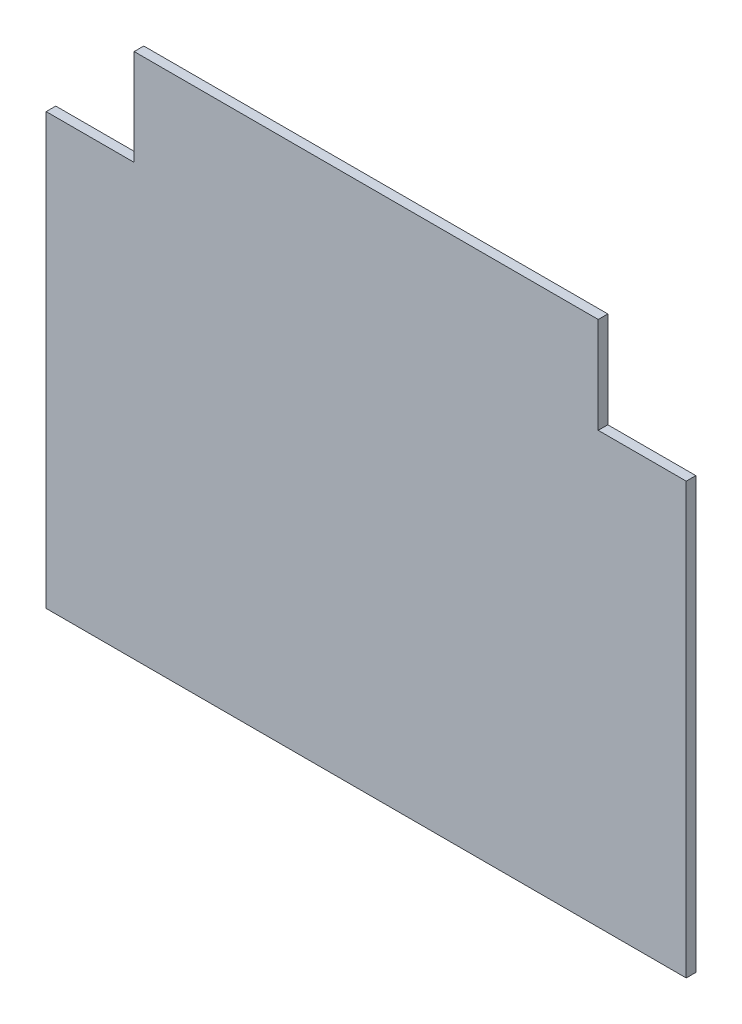
SolidWorks part; units mm, degrees
material "Pine"
ref_plane "Front Plane" through (0, 0, 0) normal (0, 0, 1) x (1, 0, 0)
ref_plane "Top Plane" through (0, 0, 0) normal (0, 1, 0) x (1, 0, 0)
ref_plane "Right Plane" through (0, 0, 0) normal (1, 0, 0) x (0, 0, -1)
sketch "Sketch1" plane through (0, 0, 0) normal (0, 0, 1) x (1, 0, 0)
  line L1 (-110.8686, 319.5768) -> (289.1314, 319.5768)
  line L2 (-110.8686, 319.5768) -> (-110.8686, -9.3332)
  line L3 (-110.8686, -9.3332) -> (289.1314, -9.3332)
  line L4 (289.1314, 319.5768) -> (289.1314, -9.3332)
  dimension "D1" = 400
  dimension "D2" = 328.91
extrude "Boss-Extrude1" add sketch "Sketch1" along normal blind 6
sketch "Sketch2" plane through (0, 0, 0) normal (0, 0, -1) x (-1, 0, 0)
  line L1 (-289.1314, 259.5768) -> (-234.1314, 259.5768)
  line L2 (-289.1314, 259.5768) -> (-289.1314, 319.5768)
  line L3 (-289.1314, 319.5768) -> (-234.1314, 319.5768)
  line L4 (-234.1314, 259.5768) -> (-234.1314, 319.5768)
  line L5 (110.8686, 259.5768) -> (55.8686, 259.5768)
  line L6 (110.8686, 259.5768) -> (110.8686, 319.5768)
  line L7 (110.8686, 319.5768) -> (55.8686, 319.5768)
  line L8 (55.8686, 259.5768) -> (55.8686, 319.5768)
  line L9 (110.8686, 319.5768) -> (110.8686, -9.3332) construction
  line L10 (-289.1314, 319.5768) -> (110.8686, 319.5768) construction
  line L11 (-289.1314, -9.3332) -> (-289.1314, 319.5768) construction
  dimension "D1" = 55
  dimension "D2" = 55
  dimension "D3" = 60
  dimension "D4" = 60
  dimension "D5" = 0
  dimension "D6" = 0
  dimension "D7" = 0
  dimension "D8" = 0
extrude "Cut-Extrude1" cut sketch "Sketch2" against normal blind 40
